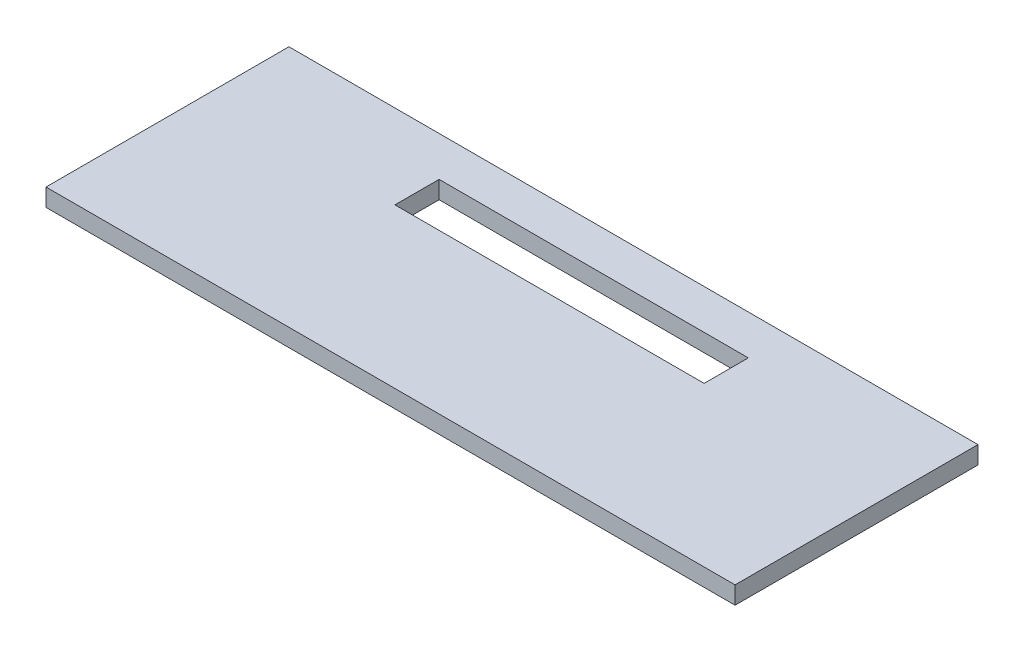
SolidWorks part; units mm, degrees
ref_plane "Front Plane" through (0, 0, 0) normal (0, 0, 1) x (1, 0, 0)
ref_plane "Top Plane" through (0, 0, 0) normal (0, 1, 0) x (1, 0, 0)
ref_plane "Right Plane" through (0, 0, 0) normal (1, 0, 0) x (0, 0, -1)
sketch "Sketch1" plane through (0, 0, 0) normal (0, 1, 0) x (1, 0, 0)
  line L1 (-78, 27.5) -> (78, 27.5)
  line L2 (-78, 27.5) -> (-78, -27.5)
  line L3 (-78, -27.5) -> (78, -27.5)
  line L4 (78, 27.5) -> (78, -27.5)
  line L5 (-78, 27.5) -> (78, -27.5) construction
  line L6 (-78, -27.5) -> (78, 27.5) construction
  line L7 (-35, 18.5) -> (35, 18.5)
  line L8 (-35, 18.5) -> (-35, 8.5)
  line L9 (-35, 8.5) -> (35, 8.5)
  line L10 (35, 18.5) -> (35, 8.5)
  point P0 (0, 0)
  dimension "D1" = 55
  dimension "D2" = 156
  dimension "D3" = 43
  dimension "D4" = 70
  dimension "D5" = 43
  dimension "D6" = 10
  dimension "D7" = 9
extrude "Boss-Extrude1" add sketch "Sketch1" along normal blind 4
extrude "Boss-Extrude2" add sketch "Sketch1<2>" along normal blind 4
sketch "Sketch1<2>" plane through (0, 0, 0) normal (0, 1, 0) x (1, 0, 0) same geometry as "Sketch1"
